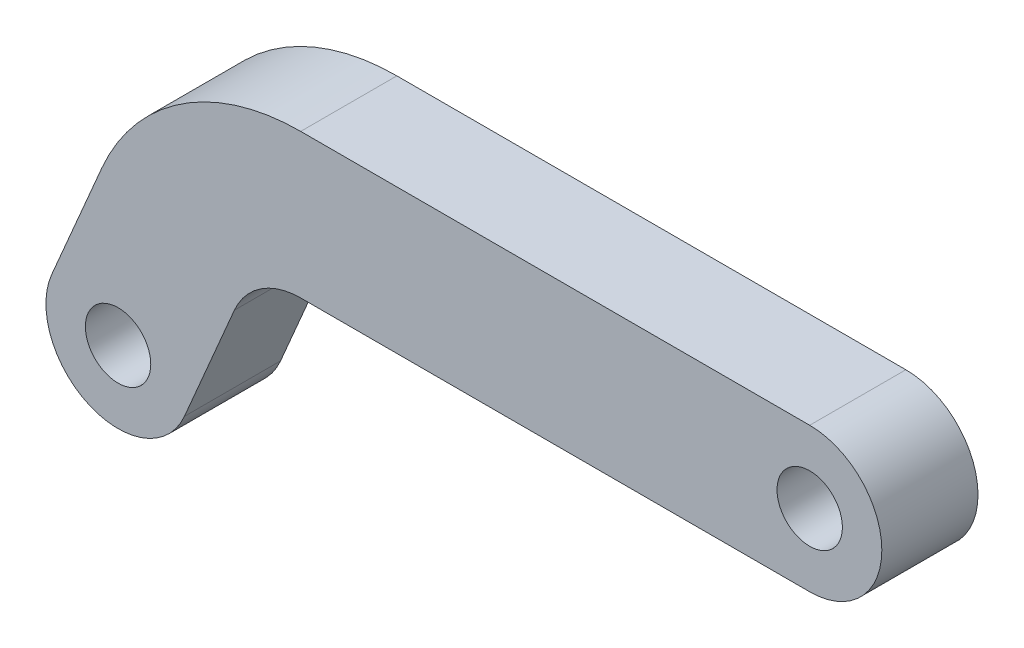
SolidWorks part; units mm, degrees
ref_plane "Front Plane" through (0, 0, 0) normal (0, 0, 1) x (1, 0, 0)
ref_plane "Top Plane" through (0, 0, 0) normal (0, 1, 0) x (1, 0, 0)
ref_plane "Right Plane" through (0, 0, 0) normal (1, 0, 0) x (0, 0, -1)
sketch "Sketch1" plane through (0, 0, 0) normal (0, 0, 1) x (1, 0, 0)
  line L0 (45.67, 18.2677) -> (12.0602, 18.2677)
  line L2 (45.67, 8.7427) -> (12.0602, 8.7427)
  line L3 (4.3792, -1.872) -> (7.681, 5.8521)
  line L4 (-4.3792, 1.872) -> (-1.0773, 9.5961)
  line L5 (0, 0) -> (45.67, 13.5052) construction
  circle A0 centre (0, 0) radius 2.159
  circle A1 centre (45.67, 13.5052) radius 2.159
  arc A2 (45.67, 8.7427) -> (45.67, 18.2677) centre (45.67, 13.5052) ccw
  arc A4 (-4.3792, 1.872) -> (4.3792, -1.872) centre (0, 0) ccw
  arc A5 (12.0602, 8.7427) -> (7.681, 5.8521) centre (12.0602, 3.9802) ccw
  arc A6 (12.0602, 18.2677) -> (-1.0773, 9.5961) centre (12.0602, 3.9802) ccw
  arc A7 (12.1787, 3.6014) -> (12.0602, 3.9802) centre (0, 0) ccw construction
  point P9 (12.1787, 3.6014)
  point P15 (11.8801, 4.4893)
  point P17 (0, 0)
  point P19 (0, 0)
  point P20 (0, 0)
  point P21 (0, 0)
  dimension "D1" = 4.318
  dimension "D4" = 4.7625
  dimension "D5" = 4.7625
  dimension "D6" = 12.7
  dimension "D7" = 4.7625
  dimension "D2" = 47.625
  dimension "D3" = 0.3969
extrude "Boss-Extrude1" add sketch "Sketch1" along normal mid plane 6.35
